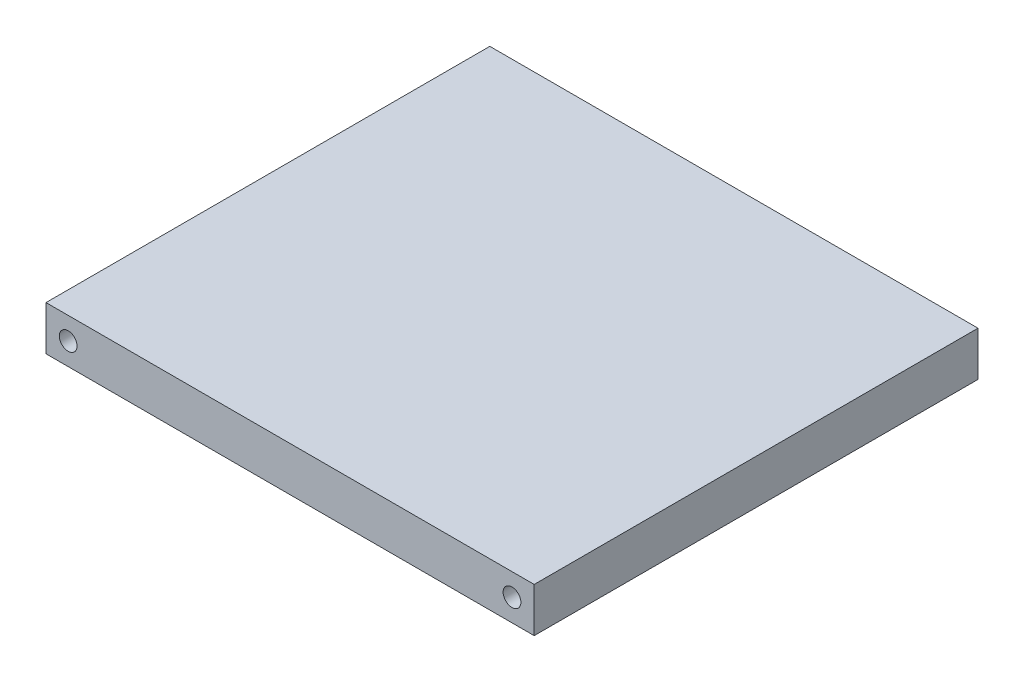
SolidWorks part; units mm, degrees
ref_plane "Front Plane" through (0, 0, 0) normal (0, 0, 1) x (1, 0, 0)
ref_plane "Top Plane" through (0, 0, 0) normal (0, 1, 0) x (1, 0, 0)
ref_plane "Right Plane" through (0, 0, 0) normal (1, 0, 0) x (0, 0, -1)
sketch "Sketch1" plane through (0, 0, 0) normal (0, 1, 0) x (1, 0, 0)
  line L1 (-55, 50) -> (55, 50)
  line L2 (-55, 50) -> (-55, -50)
  line L3 (-55, -50) -> (55, -50)
  line L4 (55, 50) -> (55, -50)
  line L5 (-55, 50) -> (55, -50) construction
  line L6 (-55, -50) -> (55, 50) construction
  point P0 (0, 0)
  dimension "D1" = 110
  dimension "D2" = 100
extrude "Boss-Extrude1" add sketch "Sketch1" along normal blind 10
sketch "Sketch2" plane through (0, 0, 50) normal (0, 0, 1) x (1, 0, 0)
  line L0 (-1050, 5) -> (48950, 5) construction
  line L1 (-55, 10) -> (-55, 0) construction
  line L2 (0, -1000) -> (0, 49000) construction
  circle A0 centre (-50, 5) radius 2
  circle A1 centre (50, 5) radius 2
  point P5 (-55, 5)
  dimension "D1" = 4
  dimension "D2" = 100
extrude "Cut-Extrude1" cut sketch "Sketch2" against normal through all
